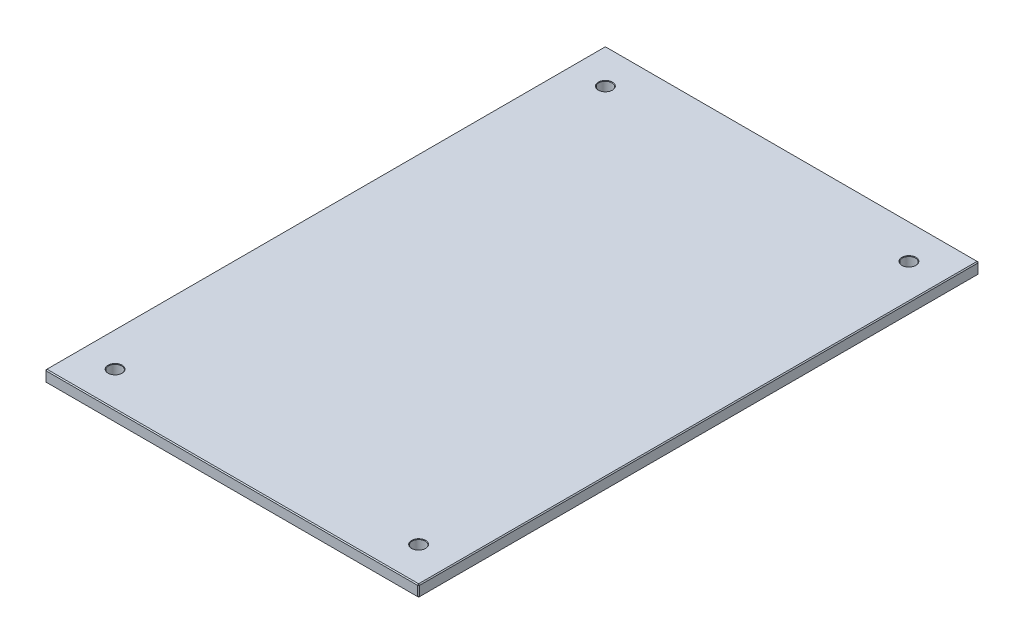
SolidWorks part; units mm, degrees
material "PC High Viscosity"
ref_plane "Front Plane" through (0, 0, 0) normal (0, 0, 1) x (1, 0, 0)
ref_plane "Top Plane" through (0, 0, 0) normal (0, 1, 0) x (1, 0, 0)
ref_plane "Right Plane" through (0, 0, 0) normal (1, 0, 0) x (0, 0, -1)
ref_axis "X Axis" through (88.99, 0, 0) along (-1, 0, 0)
ref_axis "Y Axis" through (0, 55, 0) along (0, -1, 0)
ref_axis "Z Axis" through (0, 0, -88.99) along (0, 0, 1)
sketch "Sketch1" plane through (0, 0, 0) normal (0, 1, 0) x (1, 0, 0)
  line L1 (-101.6, -152.4) -> (101.6, -152.4)
  line L2 (-101.6, -152.4) -> (-101.6, 152.4)
  line L3 (-101.6, 152.4) -> (101.6, 152.4)
  line L4 (101.6, -152.4) -> (101.6, 152.4)
  line L5 (0, 152.4) -> (0, -152.4) construction
  line L6 (-101.6, 0) -> (101.6, 0) construction
  point P0 (0, 0)
  dimension "D1" = 304.8
  dimension "D2" = 203.2
extrude "Boss-Extrude1" add sketch "Sketch1" along normal mid plane 6.35
sketch "Sketch2" plane through (0, 0, 0) normal (0, 1, 0) x (1, 0, 0)
  line L14 (-82.55, -133.35) -> (82.55, -133.35)
  line L15 (82.55, -133.35) -> (82.55, 133.35)
  line L16 (-82.55, 133.35) -> (-82.55, -133.35)
  line L17 (82.55, 133.35) -> (-82.55, 133.35)
  line L18 (-82.55, -133.35) -> (82.55, -133.35) construction
  line L19 (82.55, -133.35) -> (82.55, 133.35) construction
  line L20 (-82.55, 133.35) -> (-82.55, -133.35) construction
  line L21 (82.55, 133.35) -> (-82.55, 133.35) construction
  dimension "D1" = 19.05
sketch "Sketch6" plane through (0, 3.175, 0) normal (0, 1, 0) x (1, 0, 0)
  point P0 (-82.55, 133.35)
  point P3 (82.55, 133.35)
  point P6 (82.55, -133.35)
  point P9 (-82.55, -133.35)
hole_wizard "1/4 Clearance Hole1" positions "Sketch6" profile "Sketch4" hole size "1/4" standard "ANSI Inch" end condition through all
sketch "Sketch4" plane through (-82.55, 3.175, -133.35) normal (1, 0, 0) x (0, 0, 1)
  line L0 (0, 0) -> (0, 6.35)
  line L1 (0, 6.35) -> (3.8252, 6.35)
  line L2 (3.5712, 6.096) -> (3.5712, 0.254)
  line L3 (3.5712, 0.254) -> (3.8252, 0)
  line L5 (3.8252, 0) -> (0, 0)
  line L6 (-3.5712, 0.254) -> (-3.8252, 0) construction
  line L7 (3.8252, 6.35) -> (3.5712, 6.096)
  line L8 (-3.8252, 6.35) -> (-3.5712, 6.096) construction
  line L11 (0, -6.35) -> (0, 107.95) construction
  dimension "Thru Hole Dia." = 7.1425
  dimension "Thru Hole Depth" = 6.35
  dimension "Near C'Sink Dia." = 7.6505
  dimension "Near C'Sink Angle" = 90
  dimension "Far C'Sink Dia." = 7.6505
  dimension "Far C'Sink Angle" = 90
chamfer "Chamfer1" distance 0.508 angle 45 12 edges at (101.6, 3.175, 0) (101.6, -3.175, 0) (101.6, 0, -152.4) (0, 3.175, -152.4) (0, -3.175, -152.4) (-101.6, 0, -152.4) (-101.6, 3.175, 0) (-101.6, -3.175, 0) (-101.6, 0, 152.4) (0, 3.175, 152.4) (101.6, 0, 152.4) (0, -3.175, 152.4)
move or copy body "Body-Move/Copy1" [suppressed] bodies to move or copy 102 parameters "D1"=0, "D2"=0, "D3"=0
